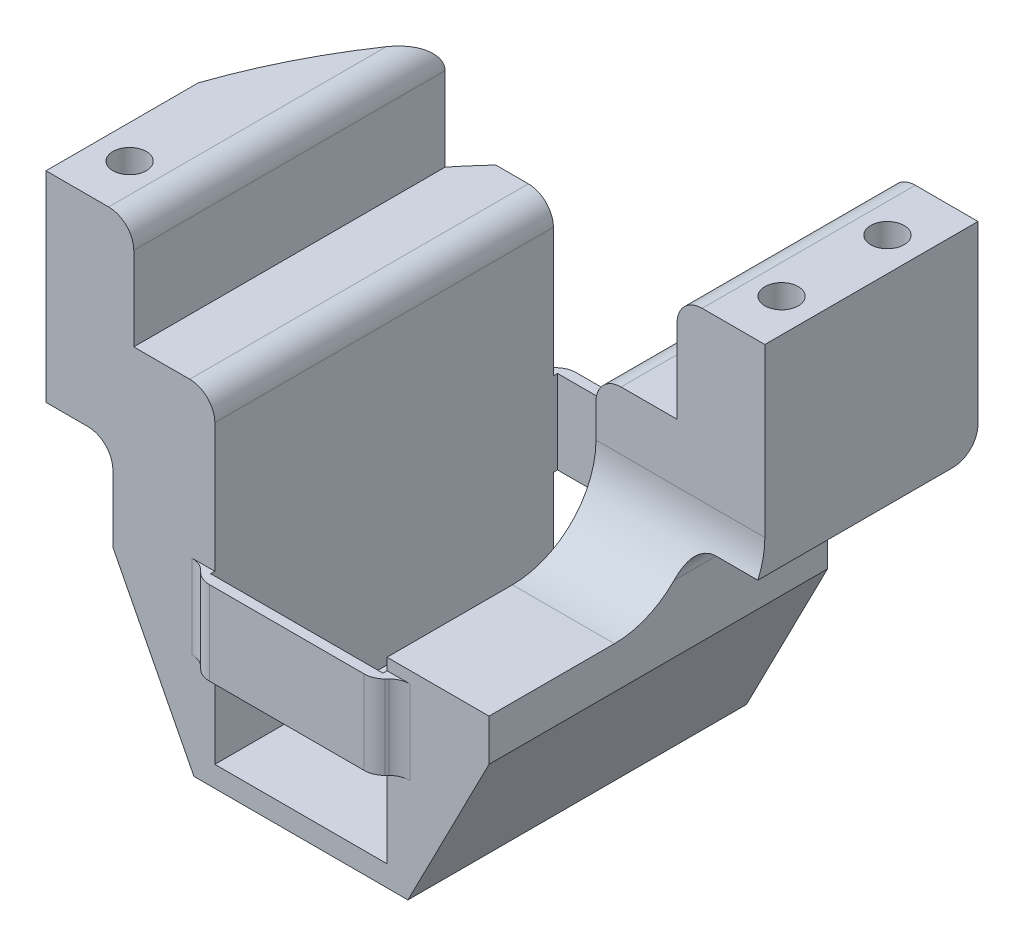
SolidWorks part; units mm, degrees
ref_plane "Front Plane" through (0, 0, 0) normal (0, 0, 1) x (1, 0, 0)
ref_plane "Top Plane" through (0, 0, 0) normal (0, 1, 0) x (1, 0, 0)
ref_plane "Right Plane" through (0, 0, 0) normal (1, 0, 0) x (0, 0, -1)
sketch "Sketch2" plane through (0, 0, 0) normal (0, 0, 1) x (1, 0, 0)
  line L18 (-22.5, 23.9) -> (-22.5, 15.9)
  line L19 (-30.5, 26.9) -> (-25.5, 26.9)
  line L20 (-30.5, 50.9) -> (-30.5, 26.9)
  line L21 (-23, 50.9) -> (-30.5, 50.9)
  line L22 (-20, 37.9) -> (-20, 47.9)
  line L23 (-13.3, 37.9) -> (-20, 37.9)
  line L24 (-10.3, -0.5) -> (-10.3, 34.9)
  line L25 (10.3, -0.5) -> (-10.3, -0.5)
  line L26 (10.3, 34.9) -> (10.3, -0.5)
  line L27 (20, 37.9) -> (13.3, 37.9)
  line L28 (20, 47.9) -> (20, 37.9)
  line L29 (30.5, 50.9) -> (23, 50.9)
  line L30 (30.5, 26.9) -> (30.5, 50.9)
  line L31 (25.5, 26.9) -> (30.5, 26.9)
  line L32 (22.5, 15.9) -> (22.5, 23.9)
  line L33 (12.8, -3) -> (22.5, 15.9)
  line L34 (-12.8, -3) -> (12.8, -3)
  line L35 (-22.5, 15.9) -> (-12.8, -3)
  line L36 (-22.5, 23.9) -> (-22.5, 15.9)
  line L37 (-30.5, 26.9) -> (-25.5, 26.9)
  line L38 (-30.5, 50.9) -> (-30.5, 26.9)
  line L39 (-23, 50.9) -> (-30.5, 50.9)
  line L40 (-20, 37.9) -> (-20, 47.9)
  line L41 (-13.3, 37.9) -> (-20, 37.9)
  line L42 (-10.3, -0.5) -> (-10.3, 34.9)
  line L43 (10.3, -0.5) -> (-10.3, -0.5)
  line L44 (10.3, 34.9) -> (10.3, -0.5)
  line L45 (20, 37.9) -> (13.3, 37.9)
  line L46 (20, 47.9) -> (20, 37.9)
  line L47 (30.5, 50.9) -> (23, 50.9)
  line L48 (30.5, 26.9) -> (30.5, 50.9)
  line L49 (25.5, 26.9) -> (30.5, 26.9)
  line L50 (22.5, 15.9) -> (22.5, 23.9)
  line L51 (12.8, -3) -> (22.5, 15.9)
  line L52 (-12.8, -3) -> (12.8, -3)
  line L53 (-22.5, 15.9) -> (-12.8, -3)
  arc A6 (-22.5, 23.9) -> (-25.5, 26.9) centre (-25.5, 23.9) ccw
  arc A7 (-20, 47.9) -> (-23, 50.9) centre (-23, 47.9) ccw
  arc A8 (-10.3, 34.9) -> (-13.3, 37.9) centre (-13.3, 34.9) ccw
  arc A9 (13.3, 37.9) -> (10.3, 34.9) centre (13.3, 34.9) ccw
  arc A10 (23, 50.9) -> (20, 47.9) centre (23, 47.9) ccw
  arc A11 (25.5, 26.9) -> (22.5, 23.9) centre (25.5, 23.9) ccw
  arc A12 (-22.5, 23.9) -> (-25.5, 26.9) centre (-25.5, 23.9) ccw
  arc A13 (-20, 47.9) -> (-23, 50.9) centre (-23, 47.9) ccw
  arc A14 (-10.3, 34.9) -> (-13.3, 37.9) centre (-13.3, 34.9) ccw
  arc A15 (13.3, 37.9) -> (10.3, 34.9) centre (13.3, 34.9) ccw
  arc A16 (23, 50.9) -> (20, 47.9) centre (23, 47.9) ccw
  arc A17 (25.5, 26.9) -> (22.5, 23.9) centre (25.5, 23.9) ccw
  dimension "D1" = 0
extrude "Boss-Extrude1" add sketch "Sketch2" against normal up to surface (40.5 mm away)
sketch "Sketch3" plane through (0, 50.9, 0) normal (0, 1, 0) x (1, 0, 0)
  line L0 (10.3, 0) -> (10.3, 25)
  line L1 (10.3, 40.5) -> (10.3, 0) construction
  line L2 (10.3, 25) -> (30.5, 25)
  line L3 (30.5, 40.5) -> (30.5, 0) construction
  line L4 (30.5, 25) -> (30.5, 0)
  line L5 (30.5, 0) -> (25.5, 0) construction
  line L6 (30.5, 0) -> (10.3, 0)
  dimension "D1" = 25
extrude "Cut-Extrude1" cut sketch "Sketch3" against normal blind 30
fillet "Fillet1" radius 10 1 edges at (16.4, 20.9, -25)
ref_plane "Plane1" through (0, 9.5, 0) normal (0, -1, 0) x (-1, 0, 0)
sketch "Sketch4" plane through (0, 9.5, 0) normal (0, -1, 0) x (-1, 0, 0)
  line L0 (-10.3, 0) -> (10.3, 0) construction
  line L1 (-10.3, 0) -> (10.3, 0) construction
  line L2 (-10.3, -0.5) -> (10.3, -0.5)
  line L3 (10.3, -0.5) -> (10.3, 0)
  line L4 (-10.3, -0.5) -> (-10.3, 0)
  line L5 (-10.3, -1.7) -> (10.3, -1.7)
  line L6 (10.3, -1.7) -> (12, 0)
  line L7 (10.3, 0) -> (13.3, 0) construction
  line L8 (10.3, 0) -> (12, 0)
  line L9 (0, 0) -> (0, -1.7) construction
  line L10 (-10.3, 0) -> (-12, 0)
  line L11 (-10.3, -1.7) -> (-12, 0)
  dimension "D3" = 45
  dimension "D1" = 0.5
  dimension "D2" = 1.2
extrude "Boss-Extrude2" add sketch "Sketch4" against normal blind 10 contours L11 L5 L6 L8 L3 L2 L4 L10 region at (0, 9.5, 1.0442)
ref_plane "Plane2" through (-30.5, 50.9, -20.25) normal (0, 0, 1) x (1, 0, 0)
mirror "Mirror1" about plane through (-30.5, 50.9, -20.25) normal (0, 0, 1) of "Boss-Extrude2"
fillet "Fillet2" radius 2.5 8 edges at (-10.3, 14.5, -42.2) (-12, 14.5, -40.5) (10.3, 14.5, -42.2) (12, 14.5, -40.5) (-12, 14.5, 0) (-10.3, 14.5, 1.7) (10.3, 14.5, 1.7) (12, 14.5, 0)
sketch "Sketch5" plane through (0, 0, -40.5) normal (0, 0, -1) x (-1, 0, 0)
  line L0 (-10.3, 27.2) -> (-10.3, 34.9)
  line L1 (-30.5, 26.9) -> (-25.5, 26.9) construction
  line L2 (-30.5, 50.9) -> (-30.5, 26.9) construction
  line L3 (-23, 50.9) -> (-30.5, 50.9) construction
  line L5 (-20, 37.9) -> (-20, 47.9) construction
  line L6 (-13.3, 37.9) -> (-20, 37.9) construction
  line L7 (-30.5, 26.9) -> (-25.5, 26.9)
  line L8 (-30.5, 50.9) -> (-30.5, 26.9)
  line L9 (-23, 50.9) -> (-30.5, 50.9)
  line L10 (-25.5, 26.9) -> (-10.3, 27.2)
  line L11 (-20, 37.9) -> (-20, 47.9)
  line L12 (-13.3, 37.9) -> (-20, 37.9)
  line L14 (-10.3, 19.5) -> (-10.3, 34.9) construction
  arc A0 (-10.3, 34.9) -> (-13.3, 37.9) centre (-13.3, 34.9) ccw construction
  arc A1 (-20, 47.9) -> (-23, 50.9) centre (-23, 47.9) ccw construction
  arc A3 (-20, 47.9) -> (-23, 50.9) centre (-23, 47.9) ccw
  arc A5 (-10.3, 34.9) -> (-13.3, 37.9) centre (-13.3, 34.9) ccw
extrude "Boss-Extrude4" add sketch "Sketch5" along normal blind 10 contours A5 L12 L11 A3 L9 L8 L7 L10 L0
sketch "Sketch6" plane through (0, -3, 0) normal (0, -1, 0) x (1, 0, 0)
  circle A0 centre (28.6434, 1.9907) radius 62.5 construction
  circle A1 centre (28.6434, 1.9907) radius 62.5
extrude "Cut-Extrude2" cut sketch "Sketch6" against normal through all both and the other way through all flip side to cut
fillet "Fillet4" radius 5 1 edges at (17.9, 27.05, -40.5)
sketch "Sketch7" plane through (0, 26.9, 0) normal (0, -1, 0) x (1, 0, 0)
  line L0 (30.5, -50.5) -> (30.5, -24.1652) construction
  line L1 (28.5, -25) -> (22.5, -25) construction
  line L2 (30.5, -37.3326) -> (22.5, -37.3326) construction
  line L4 (-30.5, -18.2159) -> (-30.5, 0) construction
  line L5 (-22.5, 0) -> (-25.5, 0) construction
  line L6 (30.5, -50.5) -> (30.5, -24.1652) construction
  circle A0 centre (26.5, -31) radius 2
  circle A1 centre (-26.5, -6) radius 2
  circle A2 centre (26.5, -43.6652) radius 2
  dimension "D1" = 4
  dimension "D6" = 4
  dimension "D2" = 4
  dimension "D3" = 6
  dimension "D4" = 4
  dimension "D5" = 6
  dimension "D7" = 8
extrude "Cut-Extrude3" cut sketch "Sketch7" against normal through all both and the other way through all
sketch "Sketch9" plane through (0, 26.9, 0) normal (0, -1, 0) x (1, 0, 0)
  circle A0 centre (-26.5, -6) radius 4
  circle A1 centre (-26.5, -6) radius 2
  circle A2 centre (-26.5, -6) radius 2 construction
  circle A3 centre (26.5, -31) radius 2
  circle A4 centre (26.5, -31) radius 2 construction
  circle A5 centre (26.5, -43.6652) radius 2
  circle A6 centre (26.5, -43.6652) radius 2 construction
  circle A7 centre (26.5, -31) radius 4
  circle A8 centre (26.5, -43.6652) radius 4
  dimension "D1" = 0
  dimension "D2" = 0
  dimension "D3" = 0
  dimension "D4" = 2
  dimension "D5" = 2
  dimension "D6" = 2
extrude "Cut-Extrude4" cut sketch "Sketch9" along normal through all
fillet "Fillet5" radius 3 2 edges at (28, 26.9, -50.5) (17.9, 27.05, -50.5)
